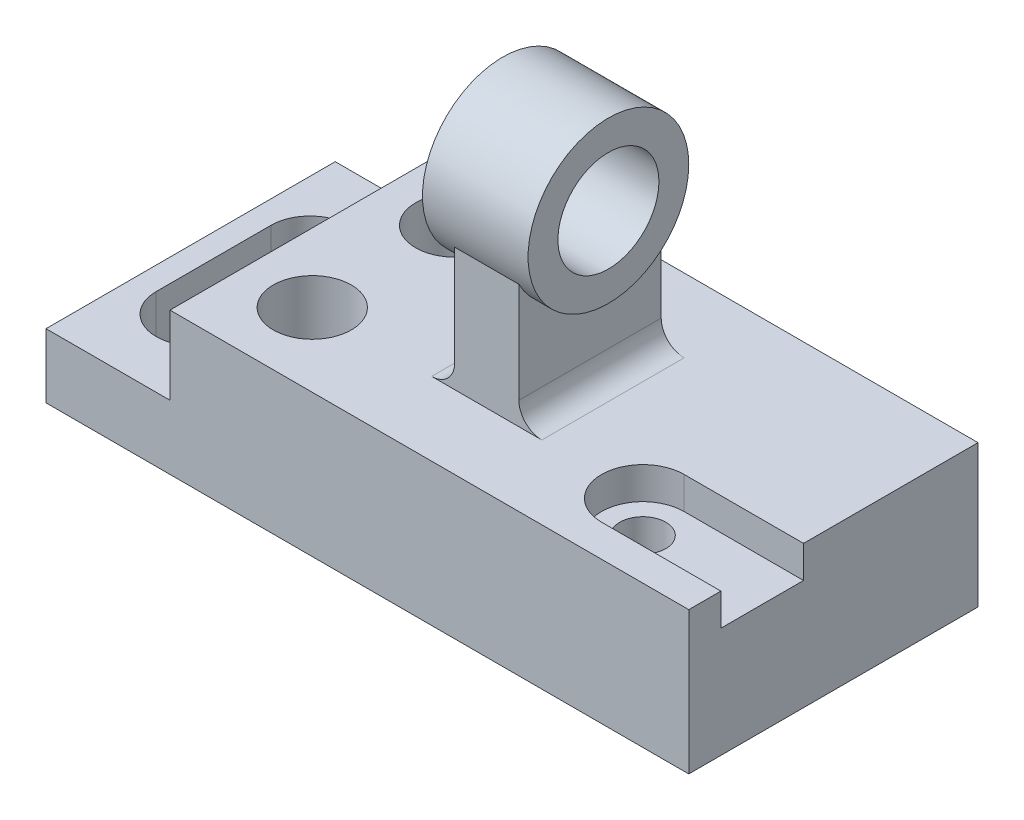
SolidWorks part; units mm, degrees
ref_plane "Front Plane" through (0, 0, 0) normal (0, 0, 1) x (1, 0, 0)
ref_plane "Top Plane" through (0, 0, 0) normal (0, 1, 0) x (1, 0, 0)
ref_plane "Right Plane" through (0, 0, 0) normal (1, 0, 0) x (0, 0, -1)
sketch "Sketch1" plane through (0, 0, 0) normal (0, 0, 1) x (1, 0, 0)
  line L0 (-112.0373, 0) -> (126.9612, 0) construction
  line L1 (0, 30.703) -> (0, -58.7741) construction
  line L8 (-73, -31) -> (67, -31)
  line L9 (67, -31) -> (67, 0)
  line L10 (67, 0) -> (-46, 0)
  line L11 (-46, 0) -> (-46, -17)
  line L12 (-46, -17) -> (-73, -17)
  line L13 (-73, -17) -> (-73, -31)
  dimension "D1" = 140
  dimension "D2" = 31
  dimension "D3" = 14
  dimension "D4" = 46
  dimension "D5" = 27
extrude "Boss-Extrude1" add sketch "Sketch1" against normal mid plane 63
sketch "Sketch3" plane through (0, 0, 0) normal (0, 1, 0) x (1, 0, 0)
  line L0 (-103.73, 0) -> (70.0786, 0) construction
  line L1 (0, 40.9453) -> (0, -48.8457) construction
  line L2 (-59.5, 12.5) -> (-59.5, -12.5) construction
  line L3 (-51, 12.5) -> (-51, -12.5)
  line L4 (-68, 12.5) -> (-68, -12.5)
  line L5 (67, -31.5) -> (-46, -31.5) construction
  line L6 (67, -24.5) -> (41, -24.5)
  line L7 (-31, 42.9204) -> (-31, -45.8071) construction
  line L8 (-46, 31.5) -> (-46, -31.5) construction
  line L10 (-73, 31.5) -> (-73, -31.5) construction
  line L11 (67, 31.5) -> (67, -31.5) construction
  line L12 (67, -6.5) -> (41, -6.5)
  line L13 (32, 4.7858) -> (32, -40.9453) construction
  line L14 (67, -6.5) -> (67, -24.5)
  arc A0 (-51, 12.5) -> (-68, 12.5) centre (-59.5, 12.5) ccw
  arc A1 (-68, -12.5) -> (-51, -12.5) centre (-59.5, -12.5) ccw
  circle A2 centre (-31, 15.5) radius 8.5
  circle A3 centre (-31, -15.5) radius 8.5
  arc A4 (41, -6.5) -> (41, -24.5) centre (41, -15.5) ccw
  circle A5 centre (41, -15.5) radius 5
  point P7 (-59.5, 0)
  line M14 (67, -31.5) -> (67, 31.5)
  dimension "D2" = 42
  dimension "D5" = 17
  dimension "D7" = 10
  dimension "D1" = 17
  dimension "D3" = 15
  dimension "D4" = 31
  dimension "D6" = 5
  dimension "D8" = 25
  dimension "D9" = 35
  dimension "D10" = 26
extrude "Cut-Extrude1" cut sketch "Sketch3" against normal through all contours A5 region at (41, 0, 15.5)
extrude "Cut-Extrude2" cut sketch "Sketch3<3>" against normal blind 7 contours L12 A4 L6 A5 M14 region at (51.8343, 0, 15.5)
sketch "Sketch3<3>" plane through (0, 0, 0) normal (0, 1, 0) x (1, 0, 0) same geometry as "Sketch3"
extrude "Cut-Extrude3" cut sketch "Sketch3<5>" against normal through all contours A2 | A3 region at (-31, 0, -15.5) region at (-31, 0, 15.5)
sketch "Sketch3<5>" plane through (0, 0, 0) normal (0, 1, 0) x (1, 0, 0) same geometry as "Sketch3"
extrude "Cut-Extrude4" cut sketch "Sketch3<6>" against normal through all contours L4 A1 L3 A0 region at (-59.5, 0, 0)
sketch "Sketch3<6>" plane through (0, 0, 0) normal (0, 1, 0) x (1, 0, 0) same geometry as "Sketch3"
sketch "Sketch4" plane through (0, -31, 0) normal (0, -1, 0) x (1, 0, 0)
  line L0 (-31, 44.4397) -> (-31, -44.4397) construction
  circle A0 centre (-31, 15.5) radius 12.5
  circle A1 centre (-31, -15.5) radius 12.5
  dimension "D1" = 25
extrude "Cut-Extrude5" cut sketch "Sketch4" against normal blind 14
ref_plane "Plane1" through (4, 0, 0) normal (1, 0, 0) x (0, 0, -1)
sketch "Sketch5" plane through (4, 0, 0) normal (1, 0, 0) x (0, 0, -1)
  line L0 (56.0041, 0) -> (-61.7248, 0) construction
  line L1 (0, 64.9753) -> (0, -58.0402) construction
  line L2 (15.5, 0) -> (15.5, 26.876)
  line L3 (-15.5, 0) -> (-15.5, 26.876)
  line L4 (-15.5, 0) -> (15.5, 0)
  circle A0 centre (0, 35) radius 17.5
  circle A1 centre (0, 35) radius 11
  point P11 (0, 0)
  dimension "D1" = 35
  dimension "D2" = 22
  dimension "D3" = 35
  dimension "D4" = 31
extrude "Boss-Extrude2" add sketch "Sketch5" along normal blind 14 and the other way blind 9 separate body contours A0 A1 region at (4, 17.995, 0)
extrude "Boss-Extrude4" add sketch "Sketch5<6>" along normal blind 10 and the other way blind 4 contours A0 L3 L4 L2 region at (4, 10.2633, 0)
sketch "Sketch5<6>" plane through (4, 0, 0) normal (1, 0, 0) x (0, 0, -1) same geometry as "Sketch5"
fillet "Fillet1" radius 5 2 edges at (14, 0, 0) (0, 0, 0)
